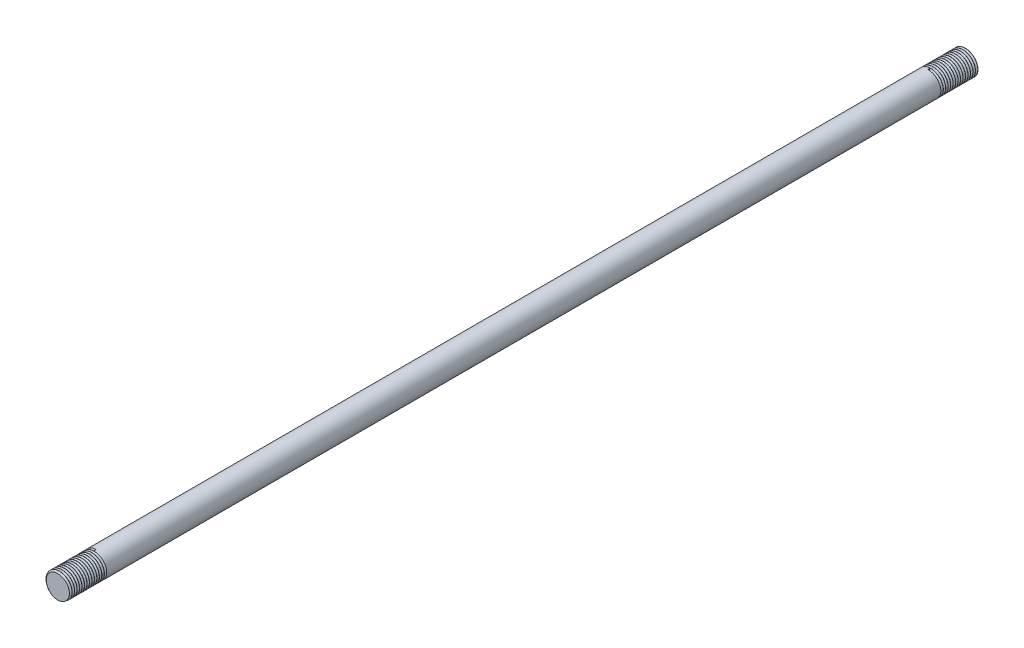
SolidWorks part; units mm, degrees
ref_plane "Front Plane" through (0, 0, 0) normal (0, 0, 1) x (1, 0, 0)
ref_plane "Top Plane" through (0, 0, 0) normal (0, 1, 0) x (1, 0, 0)
ref_plane "Right Plane" through (0, 0, 0) normal (1, 0, 0) x (0, 0, -1)
sketch "Sketch1" plane through (0, 0, 0) normal (0, 0, 1) x (1, 0, 0)
  circle A0 centre (0, 0) radius 5
  dimension "D1" = 10
extrude "Boss-Extrude1" add sketch "Sketch1" along normal blind 366.5
sketch "Sketch2" plane through (0, 0, 0) normal (0, 0, -1) x (-1, 0, 0)
  circle A0 centre (0, 0) radius 5 construction
  circle A1 centre (0, 0) radius 5
curve "Helix/Spiral1" pitch 1 height 15 radius 5 centre (0, 0, 0) axis (0, 0, 1) start towards (0, 1, 0)
ref_plane "Plane1" through (0, 5, 0) normal (-0.9995, 0, 0.0318) x (0.0318, 0, 0.9995)
sketch "Sketch3" plane through (0, 5, 0) normal (-0.9995, 0, 0.0318) x (0.0318, 0, 0.9995)
  line L1 (-0.0534, -0.8068) -> (0.4416, 0.0506)
  line L2 (0.4416, 0.0506) -> (-0.5484, 0.0506)
  line L3 (-0.5484, 0.0506) -> (-0.0534, -0.8068)
  circle A0 centre (-0.0534, -0.2352) radius 0.2858 construction
  dimension "D1" = 0.99
sweep "Cut-Sweep1" cut profiles "Sketch3" path "Helix/Spiral1" align with end faces yes
sketch "Sketch4" plane through (0, 0, 366.5) normal (0, 0, 1) x (1, 0, 0)
  circle A0 centre (0, 0) radius 5 construction
  circle A1 centre (0, 0) radius 5
curve "Helix/Spiral2" pitch 1 height 15 radius 5 centre (0, 0, 366.5) axis (0, 0, -1) start towards (0, 1, 0)
ref_plane "Plane2" through (0, 5, 366.5) normal (0.9995, 0, -0.0318) x (-0.0318, 0, -0.9995)
sketch "Sketch5" plane through (0, 5, 366.5) normal (0.9995, 0, -0.0318) x (-0.0318, 0, -0.9995)
  line L1 (-0.031, -0.7869) -> (0.464, 0.0704)
  line L2 (0.464, 0.0704) -> (-0.526, 0.0704)
  line L3 (-0.526, 0.0704) -> (-0.031, -0.7869)
  circle A0 centre (-0.031, -0.2153) radius 0.2858 construction
  dimension "D1" = 0.99
sweep "Cut-Sweep2" cut profiles "Sketch5" path "Helix/Spiral2" align with end faces yes
